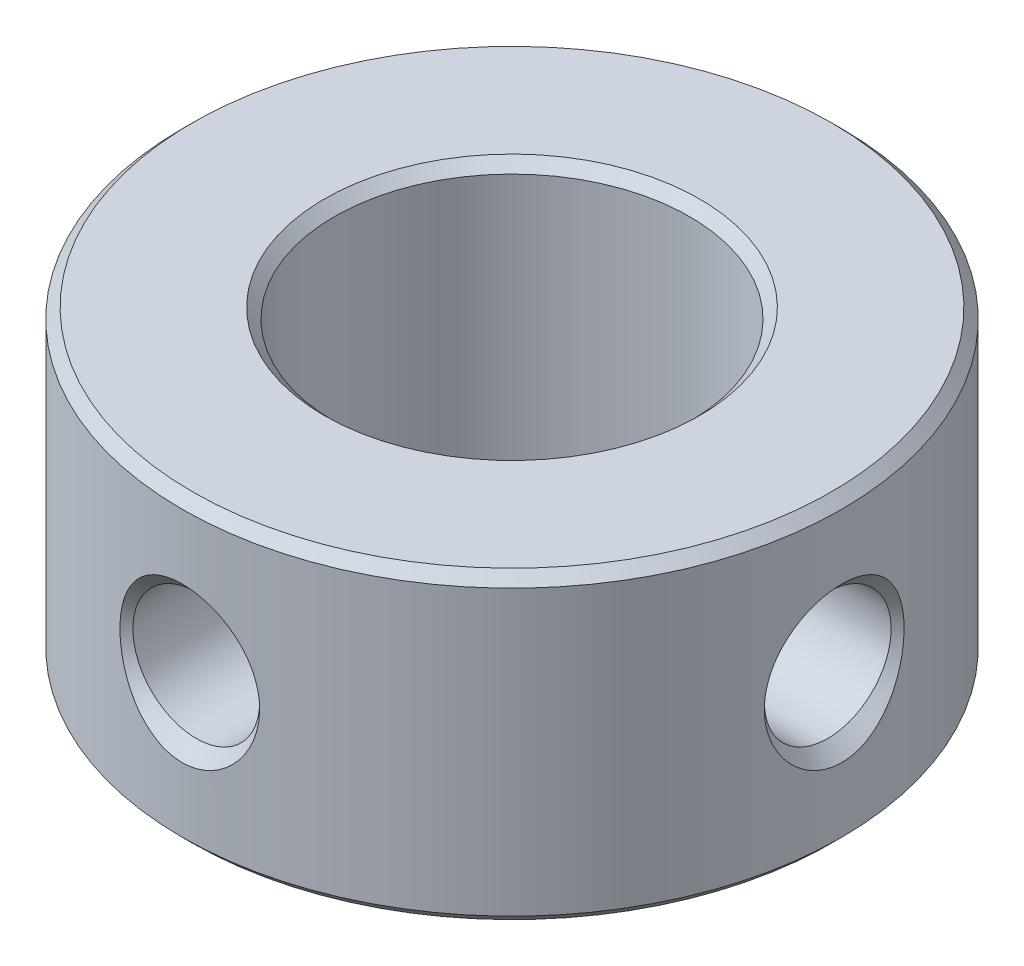
SolidWorks part; units mm, degrees
material "6061-T6 (SS)"
ref_plane "Front Plane" through (0, 0, 0) normal (0, 0, 1) x (1, 0, 0)
ref_plane "Top Plane" through (0, 0, 0) normal (0, 1, 0) x (1, 0, 0)
ref_plane "Right Plane" through (0, 0, 0) normal (1, 0, 0) x (0, 0, -1)
sketch "ProfileS" plane through (0, 0, 0) normal (0, 1, 0) x (1, 0, 0)
  circle A0 centre (0, 0) radius 3.5
  circle A1 centre (0, 0) radius 6.5
  dimension "InnerDia" = 7
  dimension "RefOuterDia" = 13
  dimension "DiaControl" = 3
extrude "Profile" add sketch "ProfileS" along normal mid plane 6
ref_plane "SetScrewPlane" through (0, 0, 6.5) normal (0, 0, 1) x (1, 0, 0)
ref_plane "SetScrewPlane2" through (6.5, 0, 0) normal (1, 0, 0) x (0, 0, -1)
hole_wizard " Tapped Hole1" positions "Sketch1" profile "Sketch2" tap size "M3x0.5" standard "ANSI Metric" end condition up to next
sketch "Sketch1" plane through (0, 0, 6.5) normal (0, 0, 1) x (1, 0, 0)
  point P0 (0, 0)
sketch "Sketch2" plane through (0, 0, 6.5) normal (1, 0, 0) x (0, -1, 0)
  line L0 (0, 0) -> (0, 13)
  line L1 (0, 13) -> (1.25, 13)
  line L2 (1.25, 13) -> (1.25, 0.275)
  line L3 (1.25, 0.275) -> (1.525, 0)
  line L5 (1.525, 0) -> (0, 0)
  line L6 (-1.25, 0.275) -> (-1.525, 0) construction
  line L11 (0, -6.35) -> (0, 107.95) construction
  dimension "Thru Tap Drill Dia." = 2.5
  dimension "Thru Tap Drill Depth" = 13
  dimension "Near C'Sink Dia." = 3.05
  dimension "Near C'Sink Angle" = 90
cosmetic thread "Hole Thread1" parameters "D2"=3
pattern_circular "CirPattern1" count 2 every 90 about axis through (0, 3, 0) along (0, -1, 0) of " Tapped Hole1" reverse direction yes
chamfer "OuterC" distance 0.2 angle 45 2 edges at (0, 3, 6.5) (0, -3, 6.5)
chamfer "InnerC" distance 0.2 angle 45 2 edges at (0, 3, 3.5) (0, -3, 3.5)
